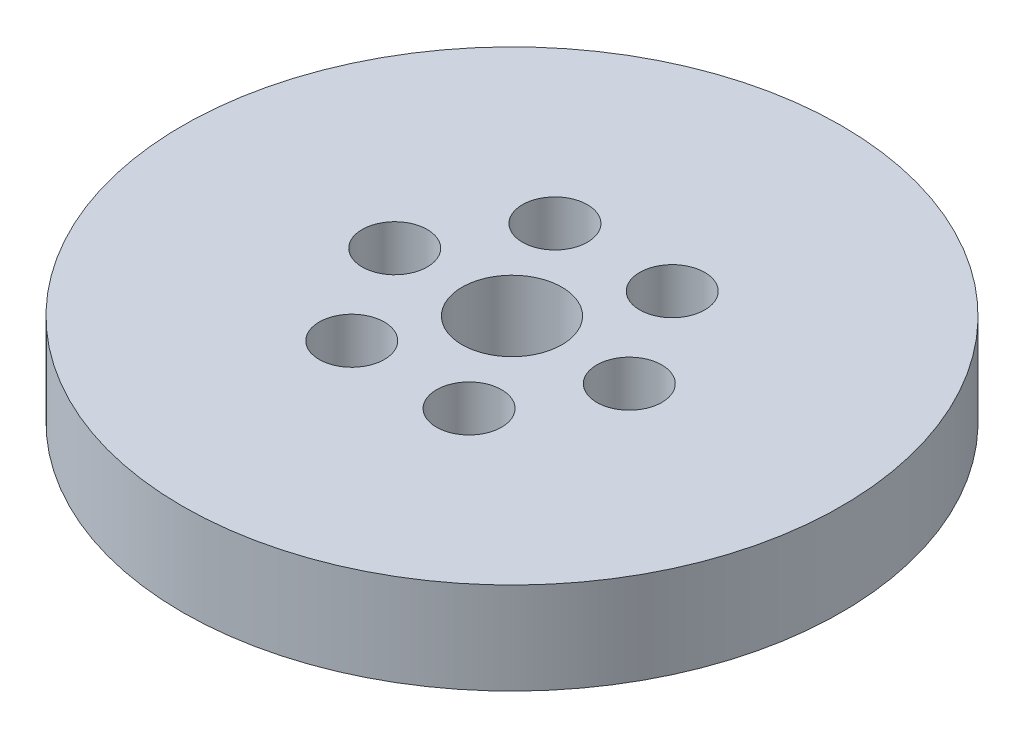
SolidWorks part; units mm, degrees
ref_plane "Front Plane" through (0, 0, 0) normal (0, 0, 1) x (1, 0, 0)
ref_plane "Top Plane" through (0, 0, 0) normal (0, 1, 0) x (1, 0, 0)
ref_plane "Right Plane" through (0, 0, 0) normal (1, 0, 0) x (0, 0, -1)
sketch "Sketch1" plane through (0, 0, 0) normal (0, 1, 0) x (1, 0, 0)
  circle A0 centre (0, 0) radius 82.5
  dimension "FLANGE_OD" = 165
extrude "Boss-Extrude1" add sketch "Sketch1" along normal blind 23
sketch "Sketch2" plane through (0, 0, 0) normal (0, 1, 0) x (1, 0, 0)
  circle A0 centre (0, 0) radius 12.5
  dimension "BORE_D" = 25
extrude "Cut-Extrude1" cut sketch "Sketch2" along normal through all
sketch "Sketch3" plane through (0, 23, 0) normal (0, 1, 0) x (1, 0, 0)
  circle A0 centre (0, 0) radius 29.3634 construction
  circle A1 centre (-29.3634, 0) radius 8.1455
  dimension "BOLT_D" = 16.2909
  dimension "BOLT_PCD" = 58.7269
extrude "Cut-Extrude2" cut sketch "Sketch3" against normal blind 20.6993
pattern_circular "CirPattern1" count 6 over 360 about axis through (0, 0, 0) along (0, 1, 0) of "Cut-Extrude2"
